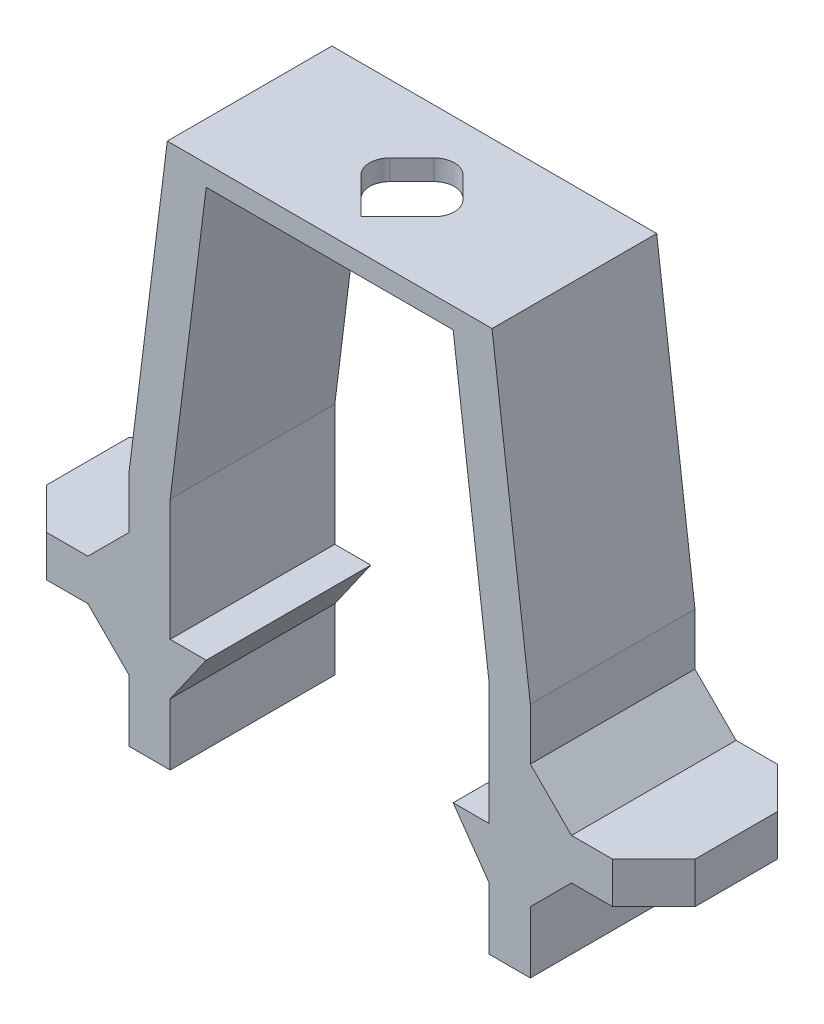
SolidWorks part; units mm, degrees
ref_plane "Front Plane" through (0, 0, 0) normal (0, 0, 1) x (1, 0, 0)
ref_plane "Top Plane" through (0, 0, 0) normal (0, 1, 0) x (1, 0, 0)
ref_plane "Right Plane" through (0, 0, 0) normal (1, 0, 0) x (0, 0, -1)
sketch "Sketch1" plane through (0, 0, 0) normal (0, 0, 1) x (1, 0, 0)
  line L0 (7.8906, 0) -> (-7.8906, 0)
  line L1 (-7.8906, 0) -> (-9.75, -14.8755)
  line L2 (-9.75, -14.8755) -> (-9.75, -26.4)
  line L3 (-9.75, -26.4) -> (-7.75, -26.4)
  line L4 (-7.75, -26.4) -> (-7.75, -23.4)
  line L5 (-7.75, -23.4) -> (-6, -20.9)
  line L6 (-6, -20.9) -> (-7.75, -20.9)
  line L7 (-7.75, -20.9) -> (-7.75, -15)
  line L8 (-7.75, -15) -> (-6, -1)
  line L9 (-6, -1) -> (6, -1)
  line L10 (0, 0) -> (0, -7.0392) construction
  line L11 (7.75, -15) -> (6, -1)
  line L12 (7.75, -20.9) -> (7.75, -15)
  line L13 (6, -20.9) -> (7.75, -20.9)
  line L14 (7.75, -23.4) -> (6, -20.9)
  line L15 (7.75, -26.4) -> (7.75, -23.4)
  line L16 (9.75, -26.4) -> (7.75, -26.4)
  line L17 (9.75, -14.8755) -> (9.75, -26.4)
  line L18 (7.8906, 0) -> (9.75, -14.8755)
  point P14 (0, 0)
  point P15 (0, 0)
  point P16 (10.2526, 0)
  point P17 (-11.8432, -2)
  point P25 (-13.3818, -19.3544)
  point P26 (-11.6931, -18.4316)
  point P27 (12, -16)
  dimension "D1" = 19.9
  dimension "D5" = 1
  dimension "D2" = 2.5
  dimension "D3" = 1.75
  dimension "D4" = 3
  dimension "D6" = 12
  dimension "D7" = 14
  dimension "D8" = 15.5
extrude "Boss-Extrude1" add sketch "Sketch1" along normal blind 8
sketch "Sketch2" plane through (0, 0, 0) normal (0, 1, 0) x (1, 0, 0)
  line L0 (0, 0) -> (0, -8) construction
  line L1 (7.8906, 0) -> (-7.8906, 0) construction
  line L2 (7.8906, -8) -> (-7.8906, -8) construction
  line L3 (0, -6.4749) -> (2.4749, -4)
  line L4 (0, -6.4749) -> (-2.4749, -4)
  line L5 (2.4749, -4) -> (0, -1.5251)
  line L6 (-2.4749, -4) -> (0, -1.5251)
  line L7 (0, -6.4749) -> (0, -1.5251) construction
  line L8 (2.4749, -4) -> (-2.4749, -4) construction
  point P0 (0, 0)
  point P1 (0, -4)
  point P8 (0, -4)
  dimension "D1" = 3.5
extrude "Cut-Extrude1" cut sketch "Sketch2" against normal through all
sketch "Sketch3" plane through (0, 0, 8) normal (0, 0, 1) x (1, 0, 0)
  line L0 (-11.75, -19.4) -> (-15.75, -19.4)
  line L1 (-15.75, -19.4) -> (-15.75, -21.4)
  line L2 (-15.75, -21.4) -> (-11.75, -21.4)
  line L3 (-11.75, -21.4) -> (-9.75, -23.4)
  line L4 (-9.75, -14.8755) -> (-9.75, -26.4) construction
  line L5 (-9.75, -23.4) -> (-9.75, -17.4)
  line L6 (-9.75, -17.4) -> (-11.75, -19.4)
  line L7 (0, 0) -> (0, -11.0245) construction
  line L8 (9.75, -17.4) -> (11.75, -19.4)
  line L9 (9.75, -23.4) -> (9.75, -17.4)
  line L10 (11.75, -21.4) -> (9.75, -23.4)
  line L11 (15.75, -21.4) -> (11.75, -21.4)
  line L12 (15.75, -19.4) -> (15.75, -21.4)
  line L13 (11.75, -19.4) -> (15.75, -19.4)
  dimension "D1" = 45
  dimension "D2" = 6
  dimension "D3" = 2
  dimension "D4" = 3
  dimension "D5" = 2
extrude "Boss-Extrude2" add sketch "Sketch3" against normal up to surface (8 mm away) up to face at (0, -16.5417, 0)
chamfer "Chamfer1" distance 2 angle 45 4 edges at (-15.75, -20.4, 0) (-15.75, -20.4, 8) (15.75, -20.4, 0) (15.75, -20.4, 8)
fillet "Fillet1" radius 1 3 edges at (0, -0.5, 1.5251) (2.4749, -0.5, 4) (-2.4749, -0.5, 4)
